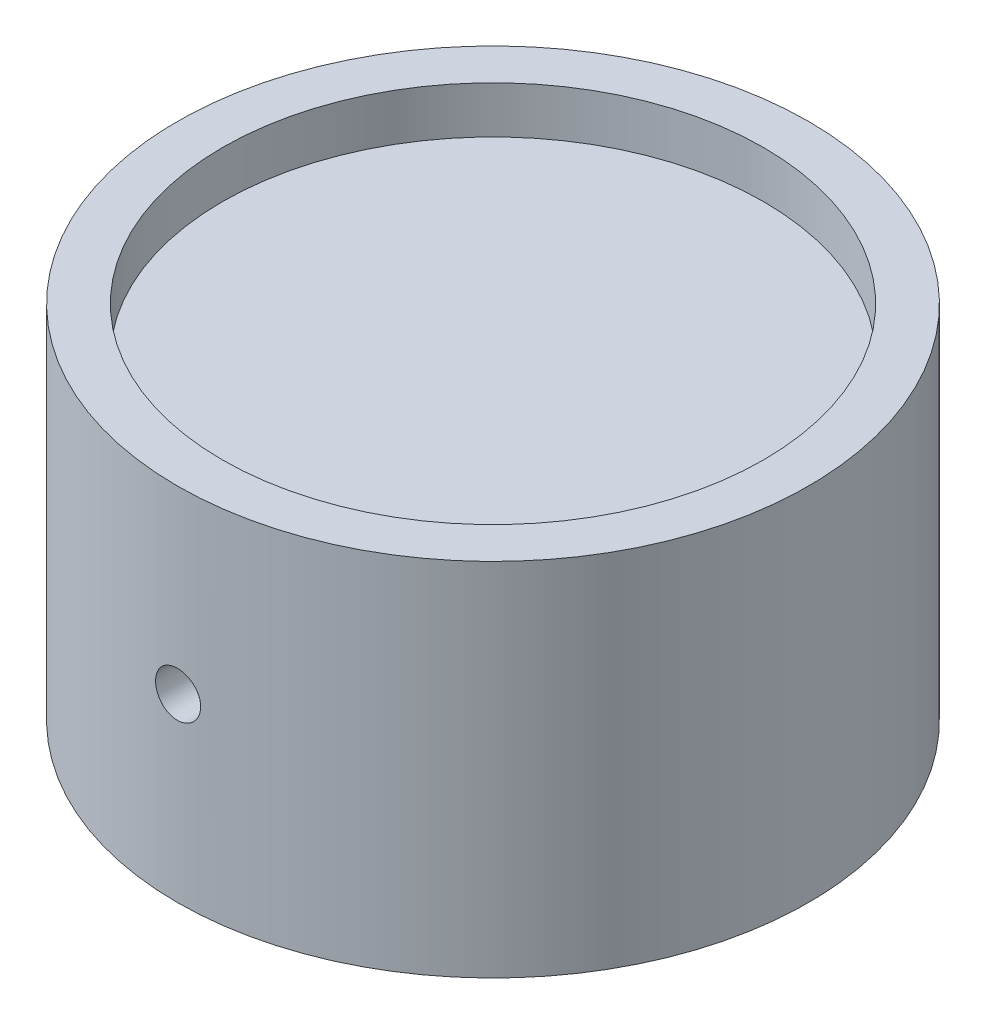
SolidWorks part; units mm, degrees
material "Cast Alloy Steel"
ref_plane "Front Plane" through (0, 0, 0) normal (0, 0, 1) x (1, 0, 0)
ref_plane "Top Plane" through (0, 0, 0) normal (0, 1, 0) x (1, 0, 0)
ref_plane "Right Plane" through (0, 0, 0) normal (1, 0, 0) x (0, 0, -1)
ref_axis "X-axis" through (-88.99, 0, 0) along (1, 0, 0)
ref_axis "Y-axis" through (0, 55, 0) along (0, -1, 0)
ref_axis "Z-axis" through (0, 0, -88.99) along (0, 0, 1)
sketch "Sketch2" plane through (0, 0, 0) normal (0, 1, 0) x (1, 0, 0)
  circle A0 centre (0, 0) radius 22.225
  dimension "D1" = 44.45
extrude "Boss-Extrude1" add sketch "Sketch2" along normal blind 25.4
hole_wizard "1/4 (1.5) Diameter Hole1" positions "Sketch3" profile "Sketch5" hole size "1/4" standard "ANSI Inch"
sketch "Sketch3" plane through (0, 25.4, 0) normal (0, 1, 0) x (1, 0, 0)
  point P0 (0, 0)
sketch "Sketch5" plane through (0, 25.4, 0) normal (1, 0, 0) x (0, 0, 1)
  line L0 (0, 0) -> (0, 3.302)
  line L1 (0, 3.302) -> (19.05, 3.302)
  line L2 (19.05, 3.302) -> (19.05, 0)
  line L5 (19.05, 0) -> (0, 0)
  line L10 (0, 3.302) -> (-19.05, 3.302) construction
  line L11 (0, -6.35) -> (0, 107.95) construction
  dimension "Hole Dia." = 38.1
  dimension "Hole Depth" = 3.302
  dimension "Drill Angle" = 180
hole_wizard "1/4 (1.5) Diameter Hole2" positions "Sketch6" profile "Sketch7" hole size "1/4" standard "ANSI Inch"
sketch "Sketch6" plane through (0, 0, 0) normal (0, -1, 0) x (-1, 0, 0)
  point P0 (0, 0)
sketch "Sketch7" plane through (0, 0, 0) normal (1, 0, 0) x (0, 0, -1)
  line L0 (0, 0) -> (0, 3.302)
  line L1 (0, 3.302) -> (19.05, 3.302)
  line L2 (19.05, 3.302) -> (19.05, 0)
  line L5 (19.05, 0) -> (0, 0)
  line L10 (0, 3.302) -> (-19.05, 3.302) construction
  line L11 (0, -6.35) -> (0, 107.95) construction
  dimension "Hole Dia." = 38.1
  dimension "Hole Depth" = 3.302
  dimension "Drill Angle" = 180
sketch "Sketch8" plane through (0, 0, 0) normal (0, 0, 1) x (1, 0, 0)
  line L0 (0, 0) -> (0, 25.4) construction
  line L1 (22.225, 25.4) -> (-22.225, 25.4) construction
  line L2 (-22.225, 12.7) -> (22.225, 12.7) construction
  line L3 (-22.225, 25.4) -> (-22.225, 0) construction
  line L4 (22.225, 0) -> (22.225, 25.4) construction
  circle A0 centre (0, 12.7) radius 1.5875
  dimension "D1" = 3.175
ref_plane "Plane1" through (0, 0, 22.225) normal (0, 0, 1) x (1, 0, 0)
hole_wizard "1/4 (0.125) Diameter Hole1" positions "Sketch10" profile "Sketch11" hole size "1/4" standard "ANSI Inch"
sketch "Sketch10" plane through (0, 0, 22.225) normal (0, 0, 1) x (1, 0, 0)
  point P0 (0, 12.7)
sketch "Sketch11" plane through (0, 12.7, 22.225) normal (1, 0, 0) x (0, -1, 0)
  line L0 (0, 0) -> (0, 16.9559)
  line L1 (0, 16.9559) -> (1.5875, 16.002)
  line L2 (1.5875, 16.002) -> (1.5875, 0)
  line L5 (1.5875, 0) -> (0, 0)
  line L10 (0, 16.9559) -> (-1.5875, 16.002) construction
  line L11 (0, -6.35) -> (0, 107.95) construction
  dimension "Hole Dia." = 3.175
  dimension "Hole Depth" = 16.002
  dimension "Drill Angle" = 118
